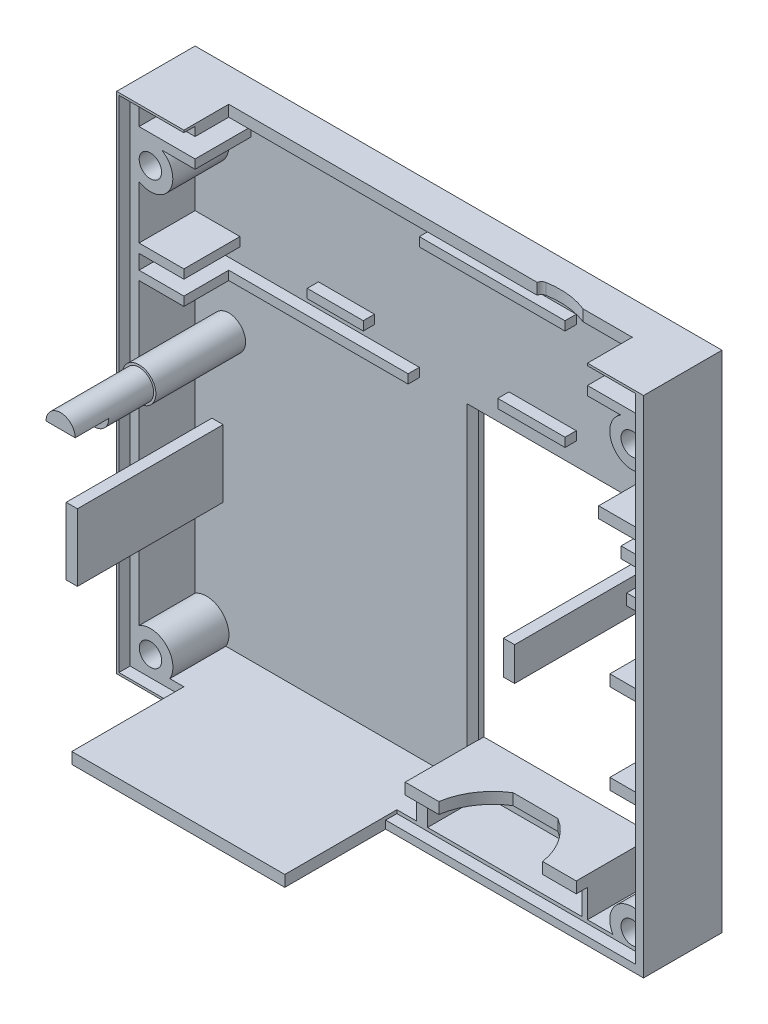
SolidWorks part; units mm, degrees
material "ABS PC"
ref_plane "Piano frontale" through (0, 0, 0) normal (0, 0, 1) x (1, 0, 0)
ref_plane "Piano superiore" through (0, 0, 0) normal (0, 1, 0) x (1, 0, 0)
ref_plane "Piano destro" through (0, 0, 0) normal (1, 0, 0) x (0, 0, -1)
sketch "Schizzo1" plane through (0, 0, 0) normal (0, 0, 1) x (1, 0, 0)
  line L1 (-23.5, -22.5) -> (23.5, -22.5)
  line L2 (-23.5, -22.5) -> (-23.5, 22.5)
  line L3 (-23.5, 22.5) -> (23.5, 22.5)
  line L4 (23.5, -22.5) -> (23.5, 22.5)
  line L5 (-23.5, -22.5) -> (23.5, 22.5) construction
  line L6 (-23.5, 22.5) -> (23.5, -22.5) construction
  point P0 (0, 0)
  dimension "D1" = 47
  dimension "D2" = 45
extrude "Estrusione-Estrusione1" add sketch "Schizzo1" along normal blind 16
sketch "Schizzo3" plane through (0, -22.5, 0) normal (0, -1, 0) x (1, 0, 0)
  line L1 (-23.5, 16) -> (-18.5, 16)
  line L2 (-23.5, 16) -> (-23.5, 7)
  line L3 (-23.5, 7) -> (-18.5, 7)
  line L4 (-18.5, 16) -> (-18.5, 7)
  line L5 (23.5, 16) -> (0.5, 16)
  line L6 (23.5, 16) -> (23.5, 7)
  line L7 (23.5, 7) -> (0.5, 7)
  line L8 (0.5, 16) -> (0.5, 7)
  dimension "D1" = 23
  dimension "D2" = 9
  dimension "D3" = 9
  dimension "D4" = 5
extrude "Taglio-Estrusione1" cut sketch "Schizzo3" against normal through all
sketch "Schizzo4" plane through (-18.5, 0, 0) normal (-1, 0, 0) x (0, 0, 1)
  line L0 (16, 22.5) -> (16, -22.5) construction
  line L1 (16, -21.5) -> (7, -21.5)
  line L2 (16, -21.5) -> (16, 22.5)
  line L3 (16, 22.5) -> (7, 22.5)
  line L12 (7, -21.5) -> (7, 22.5)
  line L13 (7, -22.5) -> (16, -22.5) construction
  dimension "D1" = 1
extrude "Taglio-Estrusione2" cut sketch "Schizzo4" against normal up to next
sketch "Schizzo5" plane through (0, 0, 7) normal (0, 0, 1) x (1, 0, 0)
  line L8 (-18.5, -21.5) -> (-18.5, -22.3)
  line L9 (-18.5, -21.5) -> (-18.5, -22.5) construction
  line L10 (-18.5, -22.3) -> (-23.3, -22.3)
  line L11 (-23.3, -22.3) -> (-23.3, 22.3)
  line L12 (-23.3, 22.3) -> (22.8, 22.3)
  line L13 (22.8, 22.3) -> (22.8, -21.8)
  line L14 (22.8, -21.8) -> (0.5, -21.8)
  line L15 (0.5, -21.8) -> (0.5, -21.5)
  line L16 (0.5, -21.5) -> (-18.5, -21.5)
  line L17 (0.5, -22.5) -> (23.5, -22.5) construction
  line L18 (23.5, 22.5) -> (23.5, -22.5) construction
  line L19 (-23.5, 22.5) -> (23.5, 22.5) construction
  line L20 (-23.5, 22.5) -> (-23.5, -22.5) construction
  line L21 (-23.5, -22.5) -> (-18.5, -22.5) construction
  line L22 (0.5, -21.5) -> (0.5, -22.5) construction
  point P21 (-20.9, -22.3)
  dimension "D1" = 0.7
  dimension "D2" = 0.7
  dimension "D3" = 0.2
  dimension "D4" = 0.2
  dimension "D5" = 0.2
extrude "Taglio-Estrusione3" cut sketch "Schizzo5" against normal blind 1
hole_wizard "Foro per Vite M3-1" positions "Schizzo9" profile "Schizzo10" hole size "M3" standard "Ansi Metric"
sketch "Schizzo9" plane through (0, 0, 6) normal (0, 0, 1) x (1, 0, 0)
  line L2 (-23.3, 22.3) -> (-23.3, -22.3) construction
  line L3 (-23.3, -22.3) -> (-18.5, -22.3) construction
  line L4 (0.5, -22.5) -> (23.5, -22.5) construction
  line L5 (23.5, 22.5) -> (23.5, -22.5) construction
  line L6 (-23.5, 22.5) -> (23.5, 22.5) construction
  line L8 (-23.5, 22.5) -> (-23.5, -22.5) construction
  point P0 (-21.49, 17.25)
  point P3 (-21.48, -20.49)
  point P6 (21.49, -20.49)
  point P9 (21.49, 17.25)
  dimension "D1" = 2.01
  dimension "D2" = 5.25
  dimension "D3" = 1.82
  dimension "D4" = 1.81
  dimension "D5" = 2.01
  dimension "D6" = 2.01
  dimension "D7" = 2.01
  dimension "D8" = 5.25
sketch "Schizzo10" plane through (-21.49, 17.25, 6) normal (1, 0, 0) x (0, -1, 0)
  line L0 (0, 0) -> (0, 4)
  line L1 (0, 4) -> (1, 4)
  line L2 (1, 4) -> (1, 0)
  line L5 (1, 0) -> (0, 0)
  line L10 (0, 4) -> (-1, 4) construction
  line L11 (0, -6.35) -> (0, 107.95) construction
  dimension "Hole Dia." = 2
  dimension "Hole Depth" = 4
  dimension "Drill Angle" = 180
shell "Svuota1" thickness 1 removed face at (-20.49, 17.25, 6)
sketch "Schizzo11" plane through (0, 0, 1) normal (0, 0, 1) x (1, 0, 0)
  line L0 (0.5, -22.5) -> (23.5, -22.5) construction
  line L1 (2.26, -18) -> (17.26, -18)
  line L2 (2.26, -18) -> (2.26, 8)
  line L3 (2.26, 8) -> (17.26, 8)
  line L4 (17.26, -18) -> (17.26, 8)
  line L5 (2.26, -18) -> (17.26, 8) construction
  line L6 (2.26, 8) -> (17.26, -18) construction
  line L7 (23.5, -22.5) -> (23.5, 22.5) construction
  point P0 (9.76, -5)
  dimension "D1" = 15
  dimension "D2" = 26
  dimension "D3" = 4.5
  dimension "D4" = 6.24
extrude "Taglio-Estrusione4" cut sketch "Schizzo11" against normal through all
sketch "Schizzo12" plane through (0, 22.5, 0) normal (0, 1, 0) x (1, 0, 0)
  line L0 (-23.5, -7) -> (23.5, -7) construction
  line L1 (-17.5, -7) -> (18.5, -7)
  line L2 (-17.5, -7) -> (-17.5, -3)
  line L3 (-17.5, -3) -> (18.5, -3)
  line L4 (18.5, -7) -> (18.5, -3)
  line L5 (-23.5, -7) -> (-23.5, 0) construction
  line L6 (23.5, -7) -> (23.5, 0) construction
  line L7 (23.5, 0) -> (-23.5, 0) construction
  dimension "D1" = 6
  dimension "D2" = 5
  dimension "D3" = 3
extrude "Taglio-Estrusione5" cut sketch "Schizzo12" against normal up to surface (1 mm away) and the other way through all up to face at (0, 21.5, 3.5)
sketch "Schizzo13" plane through (0, 0, 1) normal (0, 0, 1) x (1, 0, 0)
  line L0 (17.5, -21.5) -> (17.5, -18)
  line L1 (-19.7538, -21.5) -> (19.7638, -21.5) construction
  line L2 (17.5, -18) -> (2.24, -18)
  line L3 (2.24, -18) -> (2.24, -21.5)
  line L4 (2.24, -21.5) -> (3.24, -21.5)
  line L5 (3.24, -21.5) -> (3.24, -19)
  line L6 (3.24, -19) -> (17, -19)
  line L7 (17, -19) -> (17, -21.5)
  line L8 (17, -21.5) -> (17.5, -21.5)
  line L9 (2.26, -18) -> (17.26, -18) construction
  line L10 (23.5, 22.5) -> (23.5, -22.5) construction
  dimension "D1" = 1
  dimension "D2" = 1
  dimension "D3" = 0.5
  dimension "D4" = 6
  dimension "D5" = 15.26
extrude "Estrusione-Estrusione2" add sketch "Schizzo13" along normal blind 6
sketch "Schizzo14" plane through (2.24, 0, 0) normal (-1, 0, 0) x (0, 0, 1)
  line L10 (7, -18) -> (7, -21.5) construction
  line L11 (6, -21.5) -> (7, -21.5)
  line L12 (6, -21.5) -> (6, -19)
  line L13 (6, -19) -> (7, -19)
  line L14 (7, -21.5) -> (7, -19)
  line L15 (7, -18) -> (1, -18) construction
  line L16 (6, -21.5) -> (16, -21.5) construction
  dimension "D1" = 1
  dimension "D2" = 1
extrude "Taglio-Estrusione6" cut sketch "Schizzo14" against normal up to surface (15.26 mm away) up to face at (17.5, -20.1, 4.4)
sketch "Schizzo15" plane through (0, -18, 0) normal (0, 1, 0) x (1, 0, 0)
  line L0 (17.5, -7) -> (2.24, -7) construction
  line L1 (7.87, -3) -> (11.87, -3)
  line L2 (2.26, 0) -> (17.26, 0) construction
  line L3 (2.24, -7) -> (2.24, -1) construction
  line L4 (17.5, -7) -> (17.5, -1) construction
  line L5 (9.87, -3) -> (9.87, -7) construction
  line L6 (5.24, -7) -> (14.5, -7)
  arc A0 (14.5, -7) -> (11.87, -3) centre (8.8153, -7.8731) ccw
  arc A1 (5.24, -7) -> (7.87, -3) centre (10.9247, -7.8731) cw
  point P0 (4.51, -7)
  point P1 (14.5, -7)
  point P7 (9.87, -3)
  point P15 (9.87, -7)
  dimension "D5" = 5.7514
  dimension "D1" = 3
  dimension "D2" = 2.27
  dimension "D3" = 3
  dimension "D4" = 4
extrude "Taglio-Estrusione7" cut sketch "Schizzo15" against normal up to next
chamfer "Smusso1" distance 0.5 angle 45 2 edges at (2.26, -5, 1) (17.26, -5, 1)
sketch "Schizzo16" plane through (0, 0, 1) normal (0, 0, 1) x (1, 0, 0)
  line L0 (22.5, -9.5) -> (22.5, -10.5)
  line L1 (22.5, -18.7638) -> (22.5, 15.5238) construction
  line L2 (22.5, -10.5) -> (19.5, -10.5)
  line L3 (19.5, -10.5) -> (19.5, -1.5)
  line L4 (19.5, -1.5) -> (22.5, -1.5)
  line L5 (22.5, -1.5) -> (22.5, -2.5)
  line L6 (22.5, -2.5) -> (20.5, -2.5)
  line L7 (20.5, -2.5) -> (20.5, -9.5)
  line L8 (20.5, -9.5) -> (22.5, -9.5)
  line L10 (22.5, 10.98) -> (18.5, 10.98)
  line L11 (18.5, 10.98) -> (18.5, 9.98)
  line L12 (18.5, 9.98) -> (22.5, 9.98)
  line L13 (22.5, 9.98) -> (22.5, 10.98)
  line L14 (22.5, 8.88) -> (20.5, 8.88)
  line L15 (20.5, 8.88) -> (20.5, 7.88)
  line L16 (20.5, 7.88) -> (22.5, 7.88)
  line L17 (22.5, 15.5238) -> (22.5, -18.7638) construction
  line L18 (22.5, 7.88) -> (22.5, 8.88)
  line L19 (-22.5, 8.68) -> (-2.5, 8.68)
  line L20 (-22.5, 15.5238) -> (-22.5, -18.7697) construction
  line L21 (-2.5, 8.68) -> (-2.5, 7.88)
  line L22 (-2.5, 7.88) -> (-22.5, 7.88)
  line L23 (-22.5, 7.88) -> (-22.5, 8.68)
  line L24 (-18.5, 10.78) -> (-22.5, 10.78)
  line L25 (-22.5, 10.78) -> (-22.5, 9.98)
  line L26 (-22.5, 9.98) -> (-18.5, 9.98)
  line L27 (-18.5, 9.98) -> (-18.5, 10.78)
  line L28 (-22.5, 19.7762) -> (-17.5, 19.7762)
  line L29 (-22.5, 21.5) -> (-22.5, 18.9762) construction
  line L30 (-17.5, 19.7762) -> (-17.5, 18.9762)
  line L31 (-17.5, 18.9762) -> (-22.5, 18.9762)
  line L32 (-22.5, 18.9762) -> (-22.5, 19.7762)
  line L33 (22.5, 18.9762) -> (17.5, 18.9762)
  line L34 (17.5, 18.9762) -> (17.5, 19.7762)
  line L35 (17.5, 19.7762) -> (22.5, 19.7762)
  line L36 (22.5, 18.9762) -> (22.5, 21.5) construction
  line L37 (22.5, 19.7762) -> (22.5, 18.9762)
  line L38 (0.5, -22.5) -> (23.5, -22.5) construction
  line L39 (11.5, 19.7762) -> (-1.5, 19.7762)
  line L40 (11.5, 19.7762) -> (11.5, 18.9762)
  line L41 (11.5, 18.9762) -> (-1.5, 18.9762)
  line L42 (-1.5, 19.7762) -> (-1.5, 18.9762)
  line L51 (11.5, 10.78) -> (5.5, 10.78)
  line L52 (11.5, 10.78) -> (11.5, 9.98)
  line L53 (11.5, 9.98) -> (5.5, 9.98)
  line L54 (5.5, 10.78) -> (5.5, 9.98)
  line L55 (-6.5, 10.78) -> (-11.5, 10.78)
  line L56 (-6.5, 10.78) -> (-6.5, 9.98)
  line L57 (-6.5, 9.98) -> (-11.5, 9.98)
  line L58 (-11.5, 10.78) -> (-11.5, 9.98)
  line L59 (18.5, 22.5) -> (23.5, 22.5) construction
  line L61 (22.5, 5.5) -> (21, 5.5)
  line L62 (22.5, 5.5) -> (22.5, 4.5)
  line L63 (22.5, 4.5) -> (21, 4.5)
  line L64 (21, 5.5) -> (21, 4.5)
  dimension "D1" = 1
  dimension "D2" = 1
  dimension "D3" = 1
  dimension "D4" = 3
  dimension "D5" = 12
  dimension "D6" = 9
  dimension "D7" = 1
  dimension "D8" = 1.1
  dimension "D9" = 11.52
  dimension "D10" = 2
  dimension "D11" = 4
  dimension "D12" = 2
  dimension "D13" = 5
  dimension "D14" = 5
  dimension "D15" = 4
  dimension "D16" = 20
  dimension "D17" = 7
  dimension "D18" = 7
  dimension "D19" = 12
  dimension "D20" = 5
  dimension "D21" = 13
  dimension "D22" = 6
  dimension "D23" = 1.5
  dimension "D24" = 1
  dimension "D25" = 6
  dimension "D26" = 0.8
extrude "Estrusione-Estrusione3" add sketch "Schizzo16" along normal up to surface (5 mm away) up to face at (-20.3897, 1.5267, 6)
sketch "Schizzo17" plane through (19.5, 0, 0) normal (-1, 0, 0) x (0, 0, 1)
  line L0 (6, -10.5) -> (6, -1.5) construction
  line L1 (6, -2.5) -> (2, -2.5)
  line L2 (6, -2.5) -> (6, -9.5)
  line L3 (6, -9.5) -> (2, -9.5)
  line L4 (2, -2.5) -> (2, -9.5)
  line L5 (1, -1.5) -> (1, -10.5) construction
  line L6 (6, -1.5) -> (1, -1.5) construction
  line L7 (6, -10.5) -> (1, -10.5) construction
  dimension "D1" = 1
  dimension "D2" = 1
  dimension "D3" = 1
extrude "Taglio-Estrusione8" cut sketch "Schizzo17" against normal up to next
sketch "Schizzo18" plane through (0, 19.7762, 0) normal (0, 1, 0) x (1, 0, 0)
  line L1 (11.5, -2) -> (-17.5, -2)
  line L2 (11.5, -2) -> (11.5, -6)
  line L3 (11.5, -6) -> (-17.5, -6)
  line L4 (-17.5, -2) -> (-17.5, -6)
  line L5 (-1.5, -6) -> (11.5, -6) construction
  line L6 (11.5, -1) -> (-1.5, -1) construction
  line L9 (11.5, -6) -> (11.5, -1) construction
  line L11 (-17.5, -6) -> (-17.5, -1) construction
  dimension "D1" = 1
extrude "Taglio-Estrusione9" cut sketch "Schizzo18" against normal up to surface (11.8962 mm away) up to face at (-12.5, 7.88, 3.5)
sketch "Schizzo19" plane through (0, 8.68, 0) normal (0, 1, 0) x (1, 0, 0)
  line L0 (-22.5, -6) -> (-17.5, -6) construction
  line L1 (-17.5, -2) -> (-18.5, -2)
  line L2 (-17.5, -2) -> (-17.5, -6)
  line L3 (-17.5, -6) -> (-18.5, -6)
  line L4 (-18.5, -2) -> (-18.5, -6)
  line L5 (-18.5, -6) -> (-18.5, -1) construction
extrude "Taglio-Estrusione10" cut sketch "Schizzo19" against normal up to next
sketch "Schizzo20" plane through (0, 0, 1) normal (0, 0, 1) x (1, 0, 0)
  line L0 (21, 4.5) -> (21, 5.5) construction
  line L1 (21, 6.5) -> (20, 6.5)
  line L2 (21, 6.5) -> (21, 3.5)
  line L3 (21, 3.5) -> (20, 3.5)
  line L4 (20, 6.5) -> (20, 3.5)
  line L5 (22.5, 5.5) -> (21, 5.5) construction
  line L6 (21, 4.5) -> (22.5, 4.5) construction
  line L7 (-18.5, 7.88) -> (-22.5, 7.88) construction
  line L8 (-23.5, 22.5) -> (-23.5, -22.5) construction
  circle A0 centre (-19.5, 2.88) radius 1.5
  dimension "D4" = 3
  dimension "D1" = 1
  dimension "D2" = 1
  dimension "D3" = 1
  dimension "D5" = 5
  dimension "D6" = 4
extrude "Estrusione-Estrusione4" add sketch "Schizzo20" along normal blind 15
sketch "Schizzo21" plane through (0, 0, 16) normal (0, 0, 1) x (1, 0, 0)
  circle A0 centre (-19.5, 2.88) radius 1.3
  circle A3 centre (-19.5, 2.88) radius 1.5
  circle A4 centre (-19.5, 2.88) radius 1.5
  dimension "D2" = 0.2
  dimension "D1" = 0
extrude "Taglio-Estrusione11" cut sketch "Schizzo21" against normal blind 7
sketch "Schizzo22" plane through (0, 0, 16) normal (0, 0, 1) x (1, 0, 0)
  line L0 (-20.8, 2.88) -> (-18.2, 2.88)
  circle A1 centre (-19.5, 2.88) radius 1.3
  arc A2 (-20.8, 2.88) -> (-18.2, 2.88) centre (-19.5, 2.88) ccw
  dimension "D1" = 0
extrude "Taglio-Estrusione12" cut sketch "Schizzo22" against normal blind 3
sketch "Schizzo23" plane through (0, 0, 1) normal (0, 0, 1) x (1, 0, 0)
  line L0 (-22.5, 7.88) -> (-22.5, -18.7697) construction
  line L1 (-21, -4.5) -> (-20, -4.5)
  line L2 (-21, -4.5) -> (-21, -10.5)
  line L3 (-21, -10.5) -> (-20, -10.5)
  line L4 (-20, -4.5) -> (-20, -10.5)
  line L5 (-23.5, -22.5) -> (-18.5, -22.5) construction
  dimension "D1" = 1
  dimension "D2" = 1.5
  dimension "D3" = 6
  dimension "D4" = 12
extrude "Estrusione-Estrusione5" add sketch "Schizzo23" along normal blind 13
sketch "Schizzo25" plane through (0, 22.5, 0) normal (0, 1, 0) x (1, 0, 0)
  line L2 (14.1108, -3) -> (10.0116, -3)
  line L3 (-17.5, -3) -> (18.5, -3) construction
  line L4 (23.5, -7) -> (23.5, 0) construction
  arc A1 (14.1108, -3) -> (10.4143, -2.6146) centre (11.5824, -9.3314) ccw
  arc A3 (10.4143, -2.6146) -> (10.0116, -3) centre (10.5, -3.1072) ccw
  dimension "D2" = 0.5
  dimension "D5" = 6.8176
  dimension "D1" = 4.0992
  dimension "D3" = 0.3854
  dimension "D4" = 0.4027
  dimension "D6" = 9.3892
extrude "Taglio-Estrusione14" cut sketch "Schizzo25" against normal up to next
